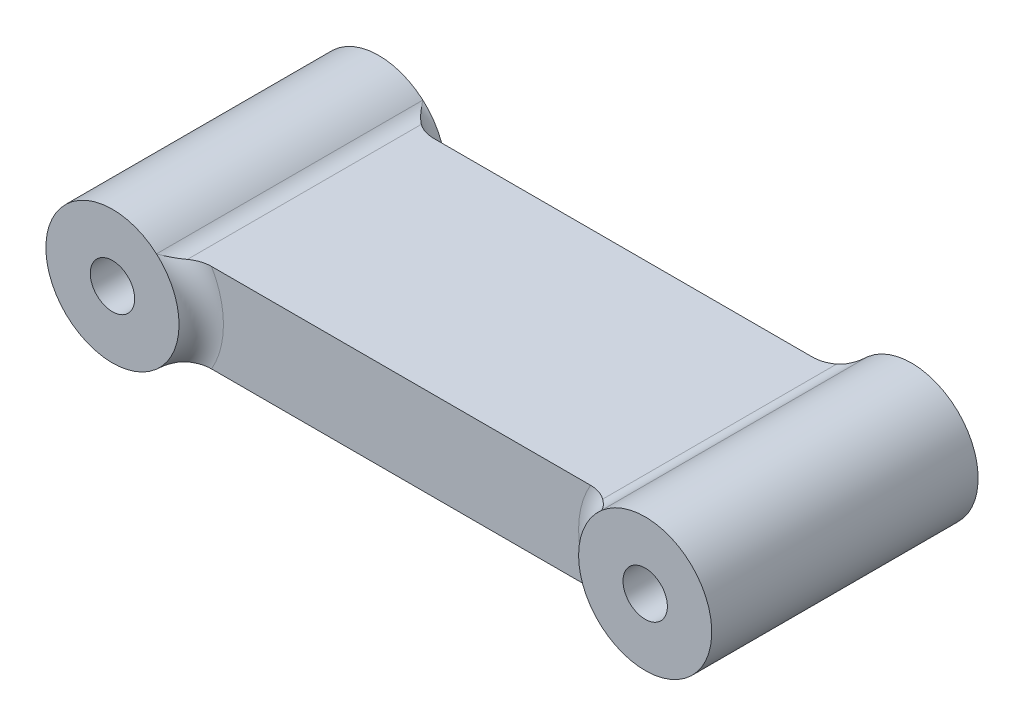
SolidWorks part; units mm, degrees
material "ABS"
ref_plane "Спереди" through (0, 0, 0) normal (0, 0, 1) x (1, 0, 0)
ref_plane "Сверху" through (0, 0, 0) normal (0, 1, 0) x (1, 0, 0)
ref_plane "Справа" through (0, 0, 0) normal (1, 0, 0) x (0, 0, -1)
sketch "Эскиз2" plane through (0, 0, 0) normal (0, 0, 1) x (1, 0, 0)
  circle A0 centre (0, 0) radius 1
  circle A1 centre (0, 0) radius 3
  dimension "D1" = 2
  dimension "D2" = 6
extrude "Бобышка-Вытянуть1" add sketch "Эскиз2" along normal mid plane 12
sketch "Эскиз4" plane through (0, 0, 0) normal (0, 0, 1) x (1, 0, 0)
  line L0 (0, 0) -> (21.5818, 0) construction
  line L1 (2.2361, 2) -> (23, 2)
  line L2 (23, 2) -> (23, -2)
  line L3 (23, -2) -> (2.2361, -2)
  arc A0 (2.2361, 2) -> (2.2361, -2) centre (0, 0) cw
  circle A1 centre (0, 0) radius 3 construction
  dimension "D1" = 4
  dimension "D2" = 23
extrude "Бобышка-Вытянуть2" add sketch "Эскиз4" along normal mid plane 10
sketch "Эскиз6" plane through (0, 0, 0) normal (0, 0, 1) x (1, 0, 0)
  line L0 (23, -2) -> (23, 2) construction
  circle A0 centre (24, 0) radius 3
  circle A1 centre (24, 0) radius 1
  point P3 (23, 0)
  dimension "D1" = 6
  dimension "D2" = 2
  dimension "D3" = 24
extrude "Бобышка-Вытянуть3" add sketch "Эскиз6" along normal mid plane 12
fillet "Скругление1" radius 1 8 edges at (2.2361, -2, 0) (3, 0, -5) (21, 0, -5) (21.7639, -2, 0) (21, 0, 5) (21.7639, 2, 0) (2.2361, 2, 0) (3, 0, 5)
sketch "Эскиз9" [suppressed] plane through (0, 0, 0) normal (0, 0, 1) x (1, 0, 0)
  line L0 (13.6542, 2.6624) -> (16.3458, 1.3376)
  line L1 (20.5359, 2) -> (3.4641, 2) construction
  point P5 (15, 2)
  point P6 (24, 0)
  dimension "D1" = 3
  dimension "D2" = 9
ref_plane "Плоскость1" [suppressed] through (3.7178, 7.5532, 0) normal (0.4416, 0.8972, 0) x (0.8972, -0.4416, 0)
